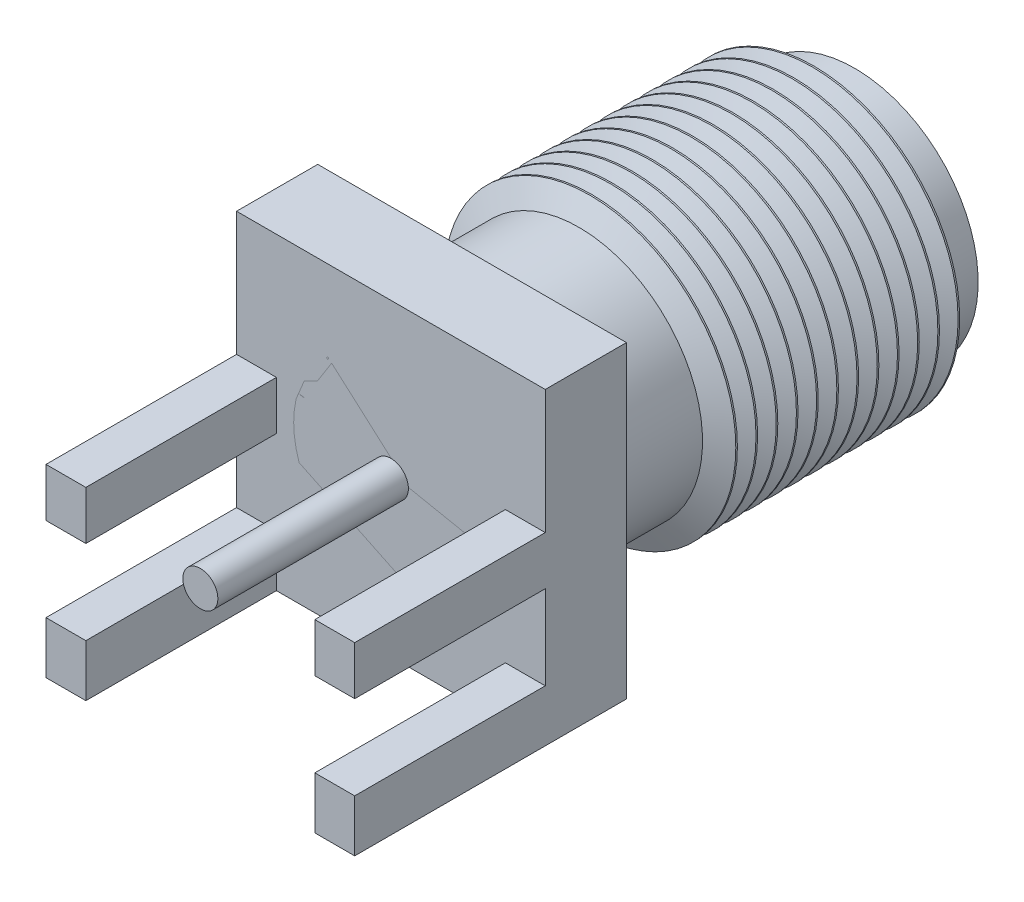
SolidWorks part; units mm, degrees
ref_plane "Front Plane" through (0, 0, 0) normal (0, 0, 1) x (1, 0, 0)
ref_plane "Top Plane" through (0, 0, 0) normal (0, 1, 0) x (1, 0, 0)
ref_plane "Right Plane" through (0, 0, 0) normal (1, 0, 0) x (0, 0, -1)
sketch "Sketch1" plane through (0, 0, 0) normal (0, 1, 0) x (1, 0, 0)
  line L1 (0, 0) -> (6.35, 0)
  line L2 (0, 0) -> (0, 1.67)
  line L3 (0, 1.67) -> (6.35, 1.67)
  line L4 (6.35, 0) -> (6.35, 1.67)
  point P5 (62.2186, 110.0656)
extrude "Boss-Extrude1" add sketch "Sketch1" along normal blind 6.35
sketch "Sketch2" plane through (0, 0, 0) normal (0, 0, 1) x (1, 0, 0)
  line L0 (0, 6.35) -> (0, 0) construction
  line L1 (0, 0) -> (0.82, 0)
  line L2 (0, 0) -> (0, 1.07)
  line L3 (0, 1.07) -> (0.82, 1.07)
  line L4 (0.82, 0) -> (0.82, 1.07)
  line L5 (6.35, 0) -> (5.53, 0)
  line L6 (6.35, 0) -> (6.35, 1.07)
  line L7 (6.35, 1.07) -> (5.53, 1.07)
  line L8 (5.53, 0) -> (5.53, 1.07)
  line L9 (0, 3.8) -> (0.82, 3.8)
  line L10 (0, 3.8) -> (0, 2.8)
  line L11 (0, 2.8) -> (0.82, 2.8)
  line L12 (0.82, 3.8) -> (0.82, 2.8)
  line L13 (6.35, 6.35) -> (6.35, 0) construction
  line L14 (6.35, 2.8) -> (5.53, 2.8)
  line L15 (6.35, 2.8) -> (6.35, 3.8)
  line L16 (6.35, 3.8) -> (5.53, 3.8)
  line L17 (5.53, 2.8) -> (5.53, 3.8)
  line L18 (0.82, 2.8) -> (0.82, 1.07) construction
  line L19 (3.175, 0) -> (3.175, 6.35) construction
  line L20 (0, 0) -> (6.35, 0) construction
  line L21 (0, 6.35) -> (6.35, 6.35) construction
  line L22 (6.35, 3.175) -> (0, 3.175) construction
  circle A0 centre (3.175, 3.175) radius 0.36
extrude "Boss-Extrude2" add sketch "Sketch2" along normal blind 3.92
sketch "Sketch3" plane through (0, 0, 0) normal (0, 0, 1) x (1, 0, 0)
  circle A0 centre (3.175, 3.175) radius 2
extrude "Boss-Extrude3" add sketch "Sketch3" against normal blind 7.5 separate body
sketch "Sketch4" plane through (0, 0, -1.67) normal (0, 0, -1) x (-1, 0, 0)
  circle A0 centre (-3.175, 3.175) radius 3
extrude "Boss-Extrude4" add sketch "Sketch4" along normal blind 7.87
ref_axis "Axis1" through (3.175, 3.175, -9.54) along (0, 0, 1)
ref_plane "Plane1" through (3.175, 0, 0) normal (1, 0, 0) x (0, 0, -1)
sketch "Sketch7" plane through (3.175, 0, 0) normal (1, 0, 0) x (0, 0, -1)
  line L0 (1.67, 6.35) -> (1.67, 5.715)
  line L1 (1.67, 5.715) -> (3.8701, 5.715)
  line L3 (3.8701, 5.715) -> (4.114, 6.2146)
  line L4 (4.114, 6.2146) -> (4.2858, 5.715)
  line L5 (4.2858, 5.715) -> (4.5297, 6.2146)
  line L6 (4.5297, 6.2146) -> (4.7015, 5.715)
  line L7 (4.7015, 5.715) -> (4.9454, 6.2146)
  line L8 (4.9454, 6.2146) -> (5.1172, 5.715)
  line L9 (5.1172, 5.715) -> (5.3611, 6.2146)
  line L10 (5.3611, 6.2146) -> (5.5328, 5.715)
  line L11 (5.5328, 5.715) -> (5.7768, 6.2146)
  line L12 (5.7768, 6.2146) -> (5.9485, 5.715)
  line L13 (5.9485, 5.715) -> (6.1924, 6.2146)
  line L14 (6.1924, 6.2146) -> (6.3642, 5.715)
  line L15 (6.3642, 5.715) -> (6.6081, 6.2146)
  line L16 (6.6081, 6.2146) -> (6.7799, 5.715)
  line L17 (6.7799, 5.715) -> (7.0238, 6.2146)
  line L18 (7.0238, 6.2146) -> (7.1956, 5.715)
  line L19 (7.1956, 5.715) -> (7.4395, 6.2146)
  line L20 (7.4395, 6.2146) -> (7.6113, 5.715)
  line L21 (7.6113, 5.715) -> (7.8552, 6.2146)
  line L22 (7.8552, 6.2146) -> (8.027, 5.715)
  line L23 (8.027, 5.715) -> (8.2709, 6.2146)
  line L24 (8.2709, 6.2146) -> (8.4427, 5.715)
  line L25 (8.4427, 5.715) -> (8.6866, 6.2146)
  line L26 (8.6866, 6.2146) -> (8.8583, 5.715)
  line L27 (8.8583, 5.715) -> (9.54, 5.715)
  line L29 (9.54, 5.715) -> (9.54, 6.35)
  line L30 (9.54, 6.35) -> (1.67, 6.35)
  line L32 (9.54, 3.175) -> (1.67, 3.175) construction
  line L33 (9.54, 0.175) -> (9.54, 6.175) construction
  line L34 (1.67, 6.35) -> (1.67, 0) construction
sketch "Sketch5" plane through (0, 0, -9.54) normal (0, 0, -1) x (-1, 0, 0)
  circle A0 centre (-3.175, 3.175) radius 2.1
extrude "Cut-Extrude1" cut sketch "Sketch5" against normal blind 2.16
sketch "Sketch6" plane through (0, 0, 3.92) normal (0, 0, 1) x (1, 0, 0)
  circle A0 centre (3.175, 3.175) radius 0.36
extrude "Boss-Extrude5" add sketch "Sketch6" against normal blind 11.43
revolve "Cut-Revolve1" cut sketch "Sketch7" angle 360 about L32
